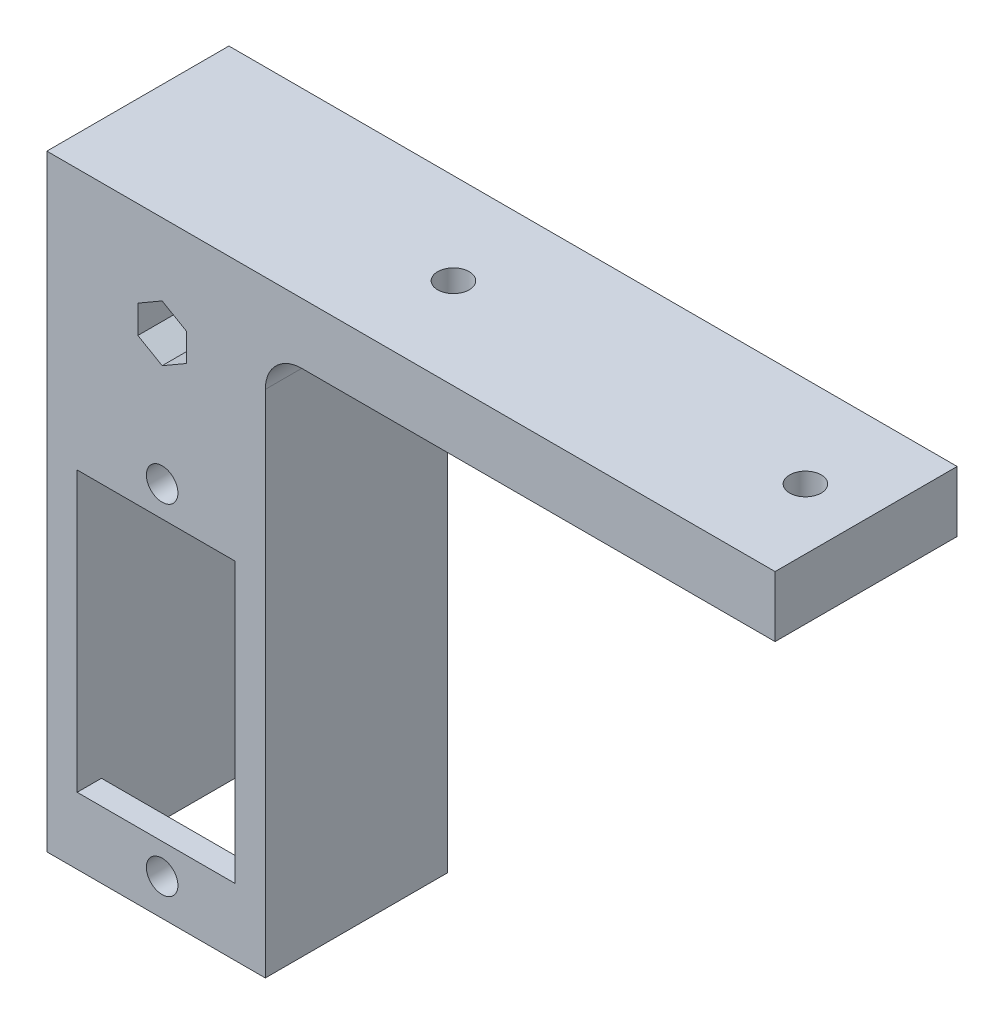
SolidWorks part; units mm, degrees
material "PLA"
ref_plane "Płaszczyzna przednia" through (0, 0, 0) normal (0, 0, 1) x (1, 0, 0)
ref_plane "Płaszczyzna górna" through (0, 0, 0) normal (0, 1, 0) x (1, 0, 0)
ref_plane "Płaszczyzna prawa" through (0, 0, 0) normal (1, 0, 0) x (0, 0, -1)
sketch "Szkic1" plane through (0, 0, 0) normal (0, 0, 1) x (1, 0, 0)
  line L15 (-30, -2.5) -> (-30, 2.5)
  line L16 (-30, 2.5) -> (30, 2.5)
  line L17 (30, -2.5) -> (30, 2.5)
  line L18 (-30, -2.5) -> (30, 2.5) construction
  line L19 (-30, 2.5) -> (30, -2.5) construction
  line L23 (-30, -2.5) -> (-30, -47.5)
  line L24 (-30, -47.5) -> (-12, -47.5)
  line L25 (-12, -47.5) -> (-12, -2.5)
  line L26 (-12, -2.5) -> (30, -2.5)
  point P0 (0, 0)
  dimension "D1" = 5
  dimension "D2" = 60
  dimension "D3" = 18
  dimension "D4" = 50
extrude "Dodanie-wyciągnięcie1" add sketch "Szkic1" along normal blind 15
hole_wizard "Otwór pod śrubę M21" positions "Szkic2" profile "Szkic3" hole size "M2" standard "ISO" end condition up to next
sketch "Szkic2" plane through (0, 2.5, 0) normal (0, -1, 0) x (-1, 0, 0)
  line L5 (-30, 0) -> (30, 0) construction
  line L7 (-30, -15) -> (-30, 0) construction
  point P0 (-25, -7.5)
  point P2 (4, -7.5)
  dimension "D1" = 29
  dimension "D2" = 5
  dimension "D3" = 7.5
sketch "Szkic3" plane through (25, 2.5, 7.5) normal (1, 0, 0) x (0, 0, 1)
  line L0 (0, 0) -> (0, 5)
  line L1 (0, 5) -> (1.3, 5)
  line L2 (1.3, 5) -> (1.3, 0)
  line L5 (1.3, 0) -> (0, 0)
  line L11 (0, -6.35) -> (0, 107.95) construction
  dimension "Średnica otworu na wylot" = 2.6
  dimension "Głębokość otworu na wylot" = 5
sketch "Szkic7" plane through (0, 0, 0) normal (0, 0, -1) x (-1, 0, 0)
  line L1 (27.5, -47.5) -> (27.5, -13.5)
  line L2 (27.5, -47.5) -> (14.5, -47.5)
  line L3 (14.5, -47.5) -> (14.5, -13.5)
  line L4 (27.5, -13.5) -> (14.5, -13.5)
  line L5 (27.5, -47.5) -> (14.5, -13.5) construction
  line L6 (14.5, -47.5) -> (27.5, -13.5) construction
  line L9 (30, -47.5) -> (12, -47.5) construction
  line L11 (30, 2.5) -> (30, -47.5) construction
  point P0 (21, -30.5)
  dimension "D1" = 34
  dimension "D2" = 13
  dimension "D3" = 9
  dimension "D4" = 17
extrude "Wytnij-wyciągnięcie2" cut sketch "Szkic7" against normal blind 13 contours L2 L3 L4 L1
sketch "Szkic8" plane through (0, 0, 13) normal (0, 0, -1) x (-1, 0, 0)
  line L0 (14.5, -47.5) -> (14.5, -13.5) construction
  line L1 (14.5, -42) -> (14.5, -19)
  line L2 (14.5, -42) -> (27.5, -42)
  line L3 (27.5, -42) -> (27.5, -19)
  line L4 (14.5, -19) -> (27.5, -19)
  line L5 (14.5, -42) -> (27.5, -19) construction
  line L6 (27.5, -42) -> (14.5, -19) construction
  line L9 (27.5, -47.5) -> (14.5, -47.5) construction
  point P0 (21, -30.5)
  dimension "D1" = 13
  dimension "D2" = 23
  dimension "D3" = 17
extrude "Wytnij-wyciągnięcie3" cut sketch "Szkic8" against normal up to next
hole_wizard "Otwór pod śrubę M22" positions "Szkic9" profile "Szkic10" hole size "M2" standard "ISO" end condition up to next
sketch "Szkic9" plane through (0, 0, 13) normal (0, 0, -1) x (-1, 0, 0)
  line L3 (14.5, -42) -> (27.5, -42) construction
  line L6 (27.5, -47.5) -> (27.5, -42) construction
  point P18 (20.5, -16.5)
  point P20 (20.5, -44.5)
  dimension "D1" = 28
  dimension "D2" = 2.5
  dimension "D3" = 7
  dimension "D4" = 7
sketch "Szkic10" plane through (-20.5, -16.5, 13) normal (1, 0, 0) x (0, 1, 0)
  line L0 (0, 0) -> (0, 2)
  line L1 (0, 2) -> (1.3, 2)
  line L2 (1.3, 2) -> (1.3, 0)
  line L5 (1.3, 0) -> (0, 0)
  line L11 (0, -6.35) -> (0, 107.95) construction
  dimension "Średnica otworu na wylot" = 2.6
  dimension "Głębokość otworu na wylot" = 2
sketch "Szkic13" plane through (0, 0, 0) normal (0, 0, -1) x (-1, 0, 0)
  circle A0 centre (20.5, -5.75) radius 3.3
  dimension "D1" = 6.6
  dimension "D2" = 30
extrude "Dodanie-wyciągnięcie2" add sketch "Szkic13" along normal blind 4
sketch "Szkic11" plane through (0, 0, -4) normal (0, 0, -1) x (-1, 0, 0)
  circle A0 centre (20.5, -5.75) radius 1.3
  dimension "D2" = 2.6
  dimension "D1" = 30
extrude "Wytnij-wyciągnięcie4" cut sketch "Szkic11" against normal up to next
sketch "Szkic12" plane through (0, 0, 15) normal (0, 0, 1) x (1, 0, 0)
  line L0 (-30, 2.5) -> (-30, -47.5) construction
  line L1 (-18.5, -6.9047) -> (-18.5, -4.5953)
  line L2 (-18.5, -4.5953) -> (-20.5, -3.4406)
  line L3 (-20.5, -3.4406) -> (-22.5, -4.5953)
  line L4 (-22.5, -4.5953) -> (-22.5, -6.9047)
  line L5 (-22.5, -6.9047) -> (-20.5, -8.0594)
  line L6 (-20.5, -8.0594) -> (-18.5, -6.9047)
  circle A0 centre (-20.5, -5.75) radius 2 construction
  dimension "D1" = 4
extrude "Wytnij-wyciągnięcie5" cut sketch "Szkic12" against normal blind 10 contours L3 L4 L5 L6 L1 L2
sketch "Szkic14" plane through (0, 2.5, 0) normal (0, 1, 0) x (1, 0, 0)
  point P0 (10.5, -7.5)
  dimension "D1" = 14.5
ref_axis "Oś1" through (10.5, 2.5, 7.5) along (0, -1, 0)
fillet "Zaokrąglenie1" radius 3 1 edges at (-12, -2.5, 7.5)
ref_plane "Blat stołu" through (0, 0, 15) normal (0, 0, 1) x (1, 0, 0)
sketch "Szkic15" plane through (0, 0, 13) normal (0, 0, -1) x (-1, 0, 0)
  point P0 (20.5, -35.75)
  dimension "D1" = 8.75
  dimension "D2" = 0
ref_axis "Oś2" through (-20.5, -35.75, 13) along (0, 0, -1)
